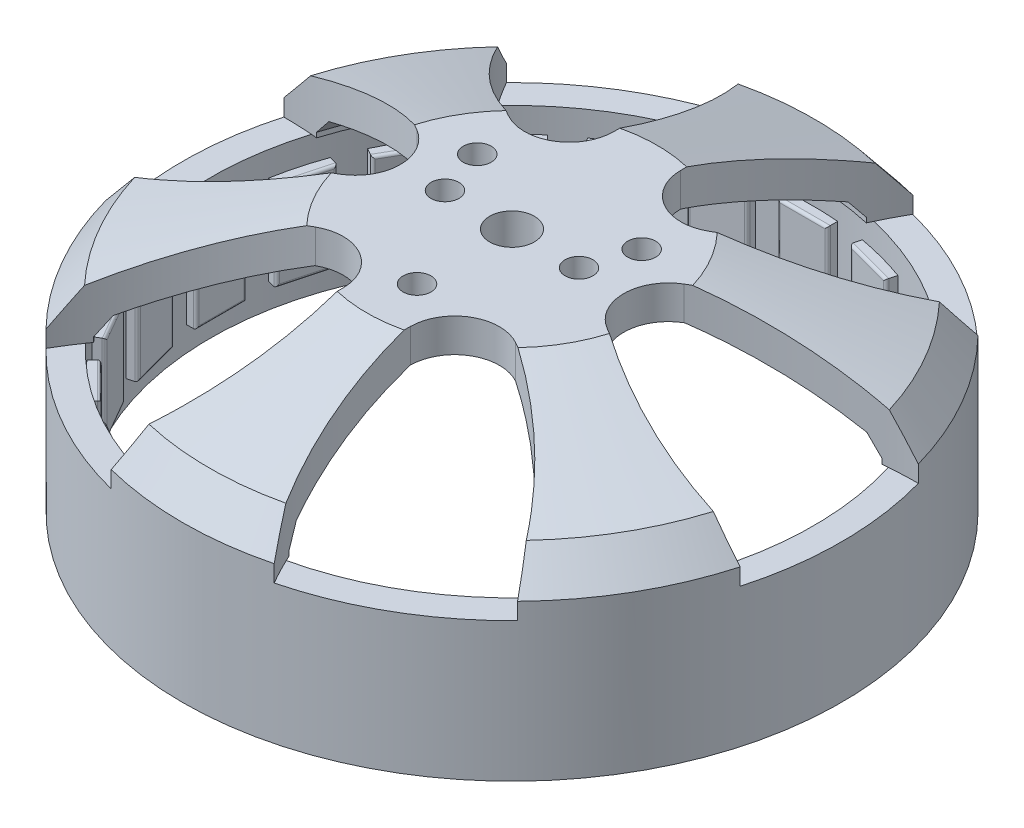
SolidWorks part; units mm, degrees
ref_plane "Front Plane" through (0, 0, 0) normal (0, 0, 1) x (1, 0, 0)
ref_plane "Top Plane" through (0, 0, 0) normal (0, 1, 0) x (1, 0, 0)
ref_plane "Right Plane" through (0, 0, 0) normal (1, 0, 0) x (0, 0, -1)
sketch "Sketch1" plane through (0, 0, 0) normal (0, 1, 0) x (1, 0, 0)
  circle A0 centre (0, 0) radius 29.5
  circle A1 centre (0, 0) radius 27
  dimension "D1" = 59
  dimension "D2" = 2.5
extrude "Boss-Extrude1" add sketch "Sketch1" along normal blind 12.45
ref_plane "Plane4" through (-27, 0, 0) normal (1, 0, 0) x (0, 0, -1)
sketch "Sketch3" plane through (-27, 0, 0) normal (1, 0, 0) x (0, 0, -1)
  line L0 (-29.5, 0) -> (29.5, 0) construction
  line L1 (-2.25, 10.225) -> (2.25, 10.225)
  line L2 (-2.25, 10.225) -> (-2.25, 2.225)
  line L3 (-2.25, 2.225) -> (2.25, 2.225)
  line L4 (2.25, 10.225) -> (2.25, 2.225)
  point P4 (2.25, 6.225)
  point P9 (0, 2.225)
  dimension "D1" = 4.5
  dimension "D2" = 8
  dimension "D3" = 6.225
extrude "Boss-Extrude2" add sketch "Sketch3" along normal mid plane 2
fillet "Fillet1" radius 0.25 4 edges at (-26, 6.225, 2.25) (-26, 6.225, -2.25) (-26, 2.225, 0) (-26, 10.225, 0)
pattern_circular "CirPattern1" count 24 over 360 about axis through (0, 12.45, 0) along (0, 1, 0) of "Fillet1", "Boss-Extrude2"
sketch "Sketch4" plane through (0, 0, 0) normal (1, 0, 0) x (0, 0, -1)
  line L1 (-27.075, 16.95) -> (-13, 21.95)
  line L2 (0, 0) -> (0, 27.3646) construction
  line L3 (-13, 21.95) -> (0, 21.95)
  line L4 (0, 21.95) -> (0, 12.45) construction
  line L5 (0, 12.45) -> (-29.5, 12.45) construction
  line L7 (-29.5, 12.45) -> (-29.5, 13.95)
  line L8 (-29.5, 13.95) -> (-27.075, 16.95)
  line L9 (-26.5, 12.45) -> (-26.5, 12.8891)
  line L10 (-26.5, 12.8891) -> (-25.2737, 14.4062)
  line L11 (-25.2737, 14.4062) -> (-12.483, 18.95)
  line L12 (-12.483, 18.95) -> (0, 18.95)
  line L13 (-29.5, 12.45) -> (-26.5, 12.45)
  line L14 (0, 18.95) -> (0, 21.95)
  dimension "D1" = 13
  dimension "D2" = 27.075
  dimension "D3" = 1.5
  dimension "D4" = 4.5
  dimension "D5" = 9.5
  dimension "D6" = 3
revolve "Revolve1" add sketch "Sketch4" angle 360 about L2
sketch "Sketch5" plane through (0, 21.95, 0) normal (0, 1, 0) x (1, 0, 0)
  line L0 (0, 0) -> (0, 48.796) construction
  line L1 (0, 0) -> (-31.6684, 0) construction
  line L2 (-14, 0) -> (-10, 0) construction
  line L3 (-28.4016, -7.975) -> (-28.4016, 7.975) construction
  line L4 (-28.4016, -7.975) -> (-30.4016, -7.975)
  line L5 (-30.4016, -7.975) -> (-30.4016, 7.975)
  line L6 (-30.4016, 7.975) -> (-28.4016, 7.975)
  arc A0 (-11.9482, -3.4337) -> (-11.9482, 3.4337) centre (-14, 0) ccw
  circle A1 centre (0, 0) radius 29.5 construction
  arc A2 (-28.4016, -7.975) -> (-11.9482, -3.4337) centre (-28.4016, 24.1012) ccw
  arc A3 (-28.4016, 7.975) -> (-11.9482, 3.4337) centre (-28.4016, -24.1012) cw
  point P15 (-28.4016, 0)
  dimension "D1" = 8
  dimension "D3" = 15.95
  dimension "D2" = 10
  dimension "D4" = 2
extrude "Cut-Extrude1" cut sketch "Sketch5" against normal blind 9.5
pattern_circular "CirPattern2" count 6 over 360 about axis through (0, 12.45, 0) along (0, -1, 0) of "Cut-Extrude1" reverse direction yes
sketch "Sketch7" plane through (0, 21.95, 0) normal (0, 1, 0) x (1, 0, 0)
  line L0 (0, 0) -> (6, 0) construction
  line L1 (0, 0) -> (0, 6.3323) construction
  circle A0 centre (0, 0) radius 2
  circle A1 centre (0, 0) radius 8.5 construction
  point P4 (0, -8.5)
  point P7 (-6, 0)
  point P8 (-7.3612, 4.25)
  point P9 (7.3612, 4.25)
  point P10 (0, 0)
  dimension "D1" = 4
  dimension "D2" = 17
  dimension "D4" = 6
  dimension "D3" = 3
hole_wizard "M3x0.5 Tapped Hole1" positions "3DSketch1" profile "Sketch8" tap size "M3x0.5" standard "ANSI Metric" end condition through all
sketch3d "3DSketch1"
  point P0 (-7.3612, 21.95, -4.25)
  point P3 (-6, 21.95, 0)
  point P6 (6, 21.95, 0)
  point P9 (7.3612, 21.95, -4.25)
  point P12 (0, 21.95, 8.5)
sketch "Sketch8" plane through (-7.3612, 21.95, -4.25) normal (1, 0, 0) x (0, 0, 1)
  line L0 (0, 0) -> (0, 21.95)
  line L1 (0, 21.95) -> (1.25, 21.95)
  line L2 (1.25, 21.95) -> (1.25, 0)
  line L5 (1.25, 0) -> (0, 0)
  line L11 (0, -6.35) -> (0, 107.95) construction
  dimension "Thru Tap Drill Dia." = 2.5
  dimension "Thru Tap Drill Depth" = 21.95
cosmetic thread "Hole Thread6" parameters "D2"=3
cosmetic thread "Hole Thread7" parameters "D2"=3
cosmetic thread "Hole Thread8" parameters "D2"=3
cosmetic thread "Hole Thread9" parameters "D2"=3
cosmetic thread "Hole Thread10" parameters "D2"=3
extrude "Cut-Extrude2" cut sketch "Sketch7" against normal blind 3
